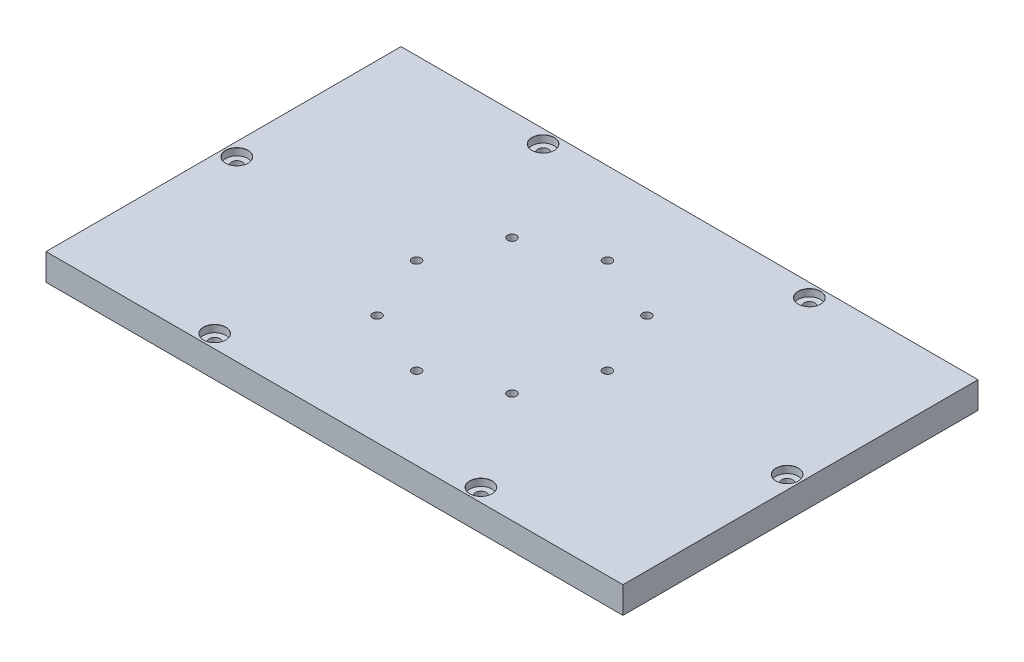
SolidWorks part; units mm, degrees
ref_plane "Ebene vorne" through (0, 0, 0) normal (0, 0, 1) x (1, 0, 0)
ref_plane "Ebene oben" through (0, 0, 0) normal (0, 1, 0) x (1, 0, 0)
ref_plane "Ebene rechts" through (0, 0, 0) normal (1, 0, 0) x (0, 0, -1)
sketch "Skizze1" plane through (0, 0, 0) normal (0, 1, 0) x (1, 0, 0)
  line L1 (0, 0) -> (130, 0)
  line L2 (0, 0) -> (0, 80)
  line L3 (0, 80) -> (130, 80)
  line L4 (130, 0) -> (130, 80)
  dimension "D1" = 80
  dimension "D2" = 130
extrude "Aufsatz-Linear austragen1" add sketch "Skizze1" along normal blind 6
hole_wizard "Ø2.4 (2.4) Durchmesser Bohrung1" positions "Skizze2" profile "Skizze3" hole size "Ø2.4" standard "DIN"
sketch "Skizze2" plane through (0, 6, 0) normal (0, 1, 0) x (1, 0, 0)
  line L0 (130, 80) -> (0, 80) construction
  line L1 (130, 0) -> (130, 80) construction
  line L2 (0, -3.3) -> (0, 3.3) construction
  line L3 (-3.3, 0) -> (3.3, 0) construction
  point P0 (35, 77)
  point P2 (95, 77)
  point P4 (127, 40)
  point P6 (95, 3)
  point P8 (35, 3)
  point P10 (3, 40)
  point P21 (133.0887, 32.8034)
  dimension "D1" = 3
  dimension "D2" = 3
  dimension "D3" = 3
  dimension "D4" = 3
  dimension "D5" = 3
  dimension "D6" = 3
  dimension "D7" = 35
  dimension "D8" = 35
  dimension "D9" = 35
  dimension "D10" = 35
  dimension "D11" = 40
  dimension "D12" = 40
sketch "Skizze3" plane through (35, 6, -77) normal (1, 0, 0) x (0, 0, 1)
  line L0 (0, 0) -> (0, 10.721)
  line L1 (0, 10.721) -> (1.2, 10)
  line L2 (1.2, 10) -> (1.2, 0.025)
  line L3 (1.2, 0.025) -> (1.225, 0)
  line L5 (1.225, 0) -> (0, 0)
  line L6 (-1.2, 0.025) -> (-1.225, 0) construction
  line L10 (0, 10.721) -> (-1.2, 10) construction
  line L11 (0, -6.35) -> (0, 107.95) construction
  dimension "Bohrerdurchmesser" = 2.4
  dimension "Bohrungstiefe" = 10
  dimension "Senkdurchmesser2 (Oben)" = 2.45
  dimension "Senkwinkel2 (Oben)" = 90
  dimension "Spitzenwinkel" = 118
hole_wizard "Stirnsenkung für M2 Flachkopfschraube mit Schlitz1" positions "Skizze6" profile "Skizze7" counterbore size "M2" standard "DIN"
sketch "Skizze6" plane through (0, 6, 0) normal (0, 1, 0) x (1, 0, 0)
  point P0 (95, 3)
  point P3 (127, 40)
  point P6 (95, 77)
  point P9 (35, 77)
  point P12 (3, 40)
  point P15 (35, 3)
sketch "Skizze7" plane through (95, 6, -3) normal (1, 0, 0) x (0, 0, 1)
  line L0 (0, 0) -> (0, 2.721)
  line L1 (0, 2.721) -> (1.2, 2)
  line L2 (1.2, 2) -> (1.2, 1.6)
  line L3 (1.2, 1.6) -> (2.5, 1.6)
  line L5 (2.5, 1.6) -> (2.5, 0.025)
  line L6 (2.5, 0.025) -> (2.525, 0)
  line L7 (2.525, 0) -> (0, 0)
  line L8 (-2.5, 0.025) -> (-2.525, 0) construction
  line L10 (0, 2.721) -> (-1.2, 2) construction
  line L11 (0, -6.35) -> (0, 107.95) construction
  dimension "Bohrerdurchmesser" = 2.4
  dimension "Bohrungstiefe" = 2
  dimension "Senkdurchmesser2" = 5
  dimension "Senktiefe2" = 1.6
  dimension "Senkdurchmesser4 (Oben)" = 5.05
  dimension "Senkwinkel2 (Oben)" = 90
  dimension "Spitzenwinkel" = 118
sketch "Skizze8" plane through (0, 6, 0) normal (0, 1, 0) x (1, 0, 0)
  line L0 (65, -24.4296) -> (65, 94.5281) construction
  line L1 (130, 0) -> (130, 80) construction
  line L3 (0, 80) -> (0, 0) construction
  line L4 (147.1504, 40) -> (-23.042, 40) construction
  line L5 (0, 0) -> (130, 0) construction
  line L6 (130, 80) -> (0, 80) construction
  circle A1 centre (43.5, 40) radius 1
  circle A2 centre (49.7972, 55.2028) radius 1
  circle A3 centre (65, 61.5) radius 1
  circle A4 centre (80.2028, 55.2028) radius 1
  circle A5 centre (86.5, 40) radius 1
  circle A6 centre (80.2028, 24.7972) radius 1
  circle A7 centre (65, 18.5) radius 1
  circle A8 centre (49.7972, 24.7972) radius 1
  point P14 (65, 40)
  point P16 (0, 0)
  dimension "D1" = 2
  dimension "D3" = 43
  dimension "D2" = 8
extrude "Schnitt-Linear austragen1" cut sketch "Skizze8" against normal up to surface (6 mm away) up to face at (35, 0, -78.2)
